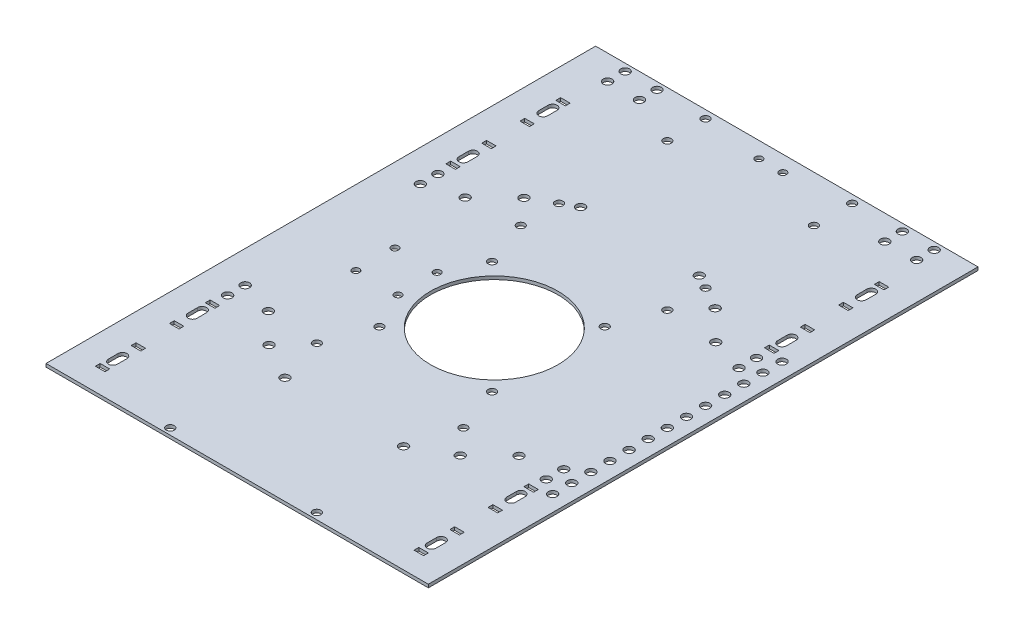
SolidWorks part; units mm, degrees
ref_plane "前视基准面" through (0, 0, 0) normal (0, 0, 1) x (1, 0, 0)
ref_plane "上视基准面" through (0, 0, 0) normal (0, 1, 0) x (1, 0, 0)
ref_plane "右视基准面" through (0, 0, 0) normal (1, 0, 0) x (0, 0, -1)
sketch "草图1" plane through (0, 0, 0) normal (0, 1, 0) x (1, 0, 0)
  line L2 (-120, 140) -> (-120, -140)
  line L3 (-120, -140) -> (120, -140)
  line L4 (120, 140) -> (120, -140)
  line L5 (-120, 140) -> (120, -140) construction
  line L6 (-120, -140) -> (120, 140) construction
  line L7 (-120, 185) -> (120, 185)
  line L8 (-120, 185) -> (-120, 140)
  line L10 (120, 185) -> (120, 140)
  line L11 (-120, 185) -> (120, 140) construction
  line L12 (-120, 140) -> (120, 185) construction
  point P0 (0, 0)
  point P6 (0, 162.5)
  dimension "D1" = 240
  dimension "D2" = 280
  dimension "D3" = 45
base flange "基体-法兰1" sketch "草图1" thickness 2 reverse thickness direction no parameters "D1"=2.7366
sketch "草图6" plane through (0, 0, 0) normal (0, 1, 0) x (1, 0, 0)
  line L0 (0, 0) -> (170.3975, 0) construction
  line L1 (0, 0) -> (0, -100) construction
  circle A0 centre (0, 0) radius 100 construction
  circle A1 centre (-60, -80) radius 2.75
  circle A2 centre (-78.6611, -61.7449) radius 2.75
  circle A3 centre (-37.25, -92.8032) radius 2.75
  circle A4 centre (37.25, -92.8032) radius 2.75
  circle A5 centre (78.6611, -61.7449) radius 2.75
  circle A6 centre (60, -80) radius 2.75
  circle A7 centre (78.6611, 61.7449) radius 2.75
  circle A8 centre (37.25, 92.8032) radius 2.75
  circle A9 centre (-60, 80) radius 2.75
  circle A10 centre (60, 80) radius 2.75
  circle A11 centre (-78.6611, 61.7449) radius 2.75
  circle A12 centre (-37.25, 92.8032) radius 2.75
  point P10 (0, 0)
  point P12 (0, 0)
  point P13 (0, 0)
  point P15 (0, 0)
  dimension "D1" = 200
  dimension "D2" = 5.5
  dimension "D3" = 80
  dimension "D4" = 2
  dimension "D5" = 2
extrude "切除-拉伸1" cut sketch "草图6" against normal blind 10 normal cut yes
sketch "草图7" plane through (0, 0, 0) normal (0, 1, 0) x (1, 0, 0)
  circle A0 centre (0, 0) radius 50 construction
  circle A1 centre (-35.3553, 35.3553) radius 2.5
  circle A2 centre (35.3553, 35.3553) radius 2.5
  circle A3 centre (35.3553, -35.3553) radius 2.5
  circle A4 centre (-35.3553, -35.3553) radius 2.5
  circle A5 centre (1.3845, 0) radius 40
  dimension "D2" = 100
  dimension "D3" = 5
  dimension "D1" = 80
  dimension "D4" = 4
extrude "切除-拉伸2" cut sketch "草图7" against normal blind 10 normal cut yes
sketch "草图9" plane through (0, 0, 0) normal (0, 1, 0) x (1, 0, 0)
  line L0 (120, -140) -> (120, 185) construction
  line L1 (-120, -140) -> (120, -140)
  line L2 (-120, -140) -> (-120, -160)
  line L3 (-120, -160) -> (120, -160)
  line L4 (120, -140) -> (120, -160)
  dimension "D1" = 20
extrude "凸台-拉伸1" add sketch "草图9" against normal blind 2
extrude "切除-拉伸3" cut sketch "草图8" against normal blind 10 normal cut yes
sketch "草图8" plane through (0, 0, 0) normal (0, 1, 0) x (1, 0, 0)
  line L0 (120, -160) -> (120, 185) construction
  line L1 (100, -110) -> (120, -110) construction
  line L2 (0, 0) -> (0, -160) construction
  line L3 (0, 0) -> (-120, 0) construction
  line L4 (-120, 185) -> (-120, -160) construction
  line L5 (100, -132) -> (100, -138) construction
  line L6 (110, -120) -> (90, -120) construction
  line L7 (110, -120) -> (110, -100) construction
  line L8 (110, -100) -> (90, -100) construction
  line L9 (90, -120) -> (90, -100) construction
  line L10 (110, -120) -> (90, -100) construction
  line L11 (110, -100) -> (90, -120) construction
  line L12 (102.8, -132) -> (102.8, -138)
  line L13 (97.2, -132) -> (97.2, -138)
  line L14 (-120, -160) -> (120, -160) construction
  line L15 (103, -146) -> (97, -146)
  line L16 (103, -146) -> (103, -143)
  line L17 (103, -143) -> (97, -143)
  line L18 (97, -146) -> (97, -143)
  line L19 (103, -146) -> (97, -143) construction
  line L20 (103, -143) -> (97, -146) construction
  line L21 (103, -123.5) -> (97, -123.5)
  line L22 (103, -123.5) -> (103, -120.5)
  line L23 (103, -120.5) -> (97, -120.5)
  line L24 (97, -123.5) -> (97, -120.5)
  line L25 (103, -123.5) -> (97, -120.5) construction
  line L26 (103, -120.5) -> (97, -123.5) construction
  line L27 (120, -160) -> (120, 185) construction
  line L28 (103, -99.5) -> (97, -96.5) construction
  line L29 (103, -96.5) -> (97, -99.5) construction
  line L30 (103, -77) -> (97, -74) construction
  line L31 (103, -74) -> (97, -77) construction
  line L32 (97, -96.5) -> (97, -99.5)
  line L33 (103, -99.5) -> (97, -99.5)
  line L34 (103, -96.5) -> (103, -99.5)
  line L35 (103, -96.5) -> (97, -96.5)
  line L36 (97, -74) -> (97, -77)
  line L37 (103, -77) -> (97, -77)
  line L38 (103, -74) -> (103, -77)
  line L39 (103, -74) -> (97, -74)
  line L40 (100, -88) -> (100, -82) construction
  line L41 (102.8, -88) -> (102.8, -82)
  line L42 (97.2, -88) -> (97.2, -82)
  arc A0 (102.8, -88) -> (97.2, -88) centre (100, -88) cw
  arc A1 (97.2, -82) -> (102.8, -82) centre (100, -82) cw
  arc A2 (102.8, -132) -> (97.2, -132) centre (100, -132) ccw
  arc A3 (97.2, -138) -> (102.8, -138) centre (100, -138) ccw
  circle A4 centre (100, -66) radius 2.75
  circle A5 centre (100, -55) radius 2.75
  point P11 (100, -110)
  point P21 (100, -135)
  point P26 (100, -144.5)
  point P31 (100, -122)
  point P44 (100, -98)
  point P45 (100, -75.5)
  point P48 (100, -85)
  dimension "D9" = 2.8
  dimension "D17" = 5.5
  dimension "D2" = 19
  dimension "D3" = 25
  dimension "D5" = 20
  dimension "D6" = 20
  dimension "D7" = 110
  dimension "D8" = 10
  dimension "D10" = 6
  dimension "D11" = 6
  dimension "D12" = 6.5
  dimension "D13" = 3
  dimension "D14" = 10
  dimension "D15" = 3
  dimension "D16" = 6
  dimension "D4" = 11
mirror "镜向1" about plane through (0, 0, 0) normal (0, 0, 1) of "切除-拉伸3"
mirror "镜向2" about plane through (0, 0, 0) normal (1, 0, 0) of "镜向1", "切除-拉伸3"
sketch "草图10" plane through (0, 0, 0) normal (0, 1, 0) x (1, 0, 0)
  line L0 (120, 185) -> (-120, 185) construction
  line L1 (-120, 185) -> (-120, -160) construction
  circle A0 centre (-97, 180.5) radius 2.75
  circle A1 centre (-77, 180.5) radius 2.75
  circle A2 centre (-97, 169.5) radius 2.75
  circle A3 centre (-77, 169.5) radius 2.75
  dimension "D3" = 5.5
  dimension "D4" = 20
  dimension "D1" = 4.5
  dimension "D2" = 23
  dimension "D5" = 2
extrude "切除-拉伸4" cut sketch "草图10" against normal blind 10 normal cut yes
mirror "镜向3" about plane through (0, 0, 0) normal (1, 0, 0) of "切除-拉伸4"
sketch "草图11" plane through (0, 0, 0) normal (0, 1, 0) x (1, 0, 0)
  line L0 (120, -160) -> (120, 185) construction
  circle A0 centre (110, 72) radius 2.75
  circle A1 centre (110, 60) radius 2.75
  circle A2 centre (110, 48) radius 2.75
  circle A3 centre (110, 36) radius 2.75
  circle A4 centre (110, 24) radius 2.75
  circle A5 centre (110, 12) radius 2.75
  circle A6 centre (110, 0) radius 2.75
  circle A7 centre (110, -12) radius 2.75
  circle A8 centre (110, -24) radius 2.75
  circle A9 centre (110, -36) radius 2.75
  circle A10 centre (110, -48) radius 2.75
  circle A11 centre (110, -60) radius 2.75
  circle A12 centre (110, -72) radius 2.75
  dimension "D2" = 5.5
  dimension "D1" = 10
  dimension "D4" = 72
  dimension "D3" = 13
extrude "切除-拉伸5" cut sketch "草图11" against normal blind 10 normal cut yes
sketch "草图12" plane through (0, 0, 0) normal (0, 1, 0) x (1, 0, 0)
  line L0 (-46.75, 0) -> (-73.25, 0) construction
  line L1 (-120, 185) -> (-120, -160) construction
  line L2 (0, 185) -> (0, 140.1837) construction
  line L3 (120, 185) -> (-120, 185) construction
  circle A0 centre (-73.25, 12.25) radius 2.25
  circle A1 centre (-73.25, -12.25) radius 2.25
  circle A2 centre (-46.75, 12.25) radius 2.25
  circle A3 centre (-46.75, -12.25) radius 2.25
  circle A4 centre (7.5, 175) radius 2.25
  circle A5 centre (-7.5, 175) radius 2.25
  point P16 (-60, 0)
  dimension "D3" = 4.5
  dimension "D5" = 4.5
  dimension "D1" = 24.5
  dimension "D4" = 60
  dimension "D6" = 15
  dimension "D7" = 10
  dimension "D8" = 26.5
  dimension "D2" = 2
extrude "切除-拉伸6" cut sketch "草图12" against normal blind 10 normal cut yes
sketch "草图13" plane through (0, 0, 0) normal (0, 1, 0) x (1, 0, 0)
  line L0 (0, 185) -> (0, 0) construction
  line L1 (0, 0) -> (-120, 0) construction
  line L2 (-46, 110) -> (0, 110) construction
  line L3 (120, 185) -> (-120, 185) construction
  line L4 (-120, 185) -> (-120, -160) construction
  circle A0 centre (-46, 156) radius 2.5
  circle A1 centre (-46, 64) radius 2.5
  circle A2 centre (46, 64) radius 2.5
  circle A3 centre (46, 156) radius 2.5
  dimension "D3" = 5
  dimension "D1" = 92
  dimension "D2" = 92
  dimension "D4" = 110
extrude "切除-拉伸7" cut sketch "草图13" against normal blind 3 normal cut yes
mirror "镜向4" about plane through (0, 0, 0) normal (0, 0, 1) of "切除-拉伸7"
sketch "草图14" plane through (0, 0, 0) normal (0, 1, 0) x (1, 0, 0)
  line L0 (-44, 134) -> (0, 134) construction
  line L1 (0, 134) -> (0, 185) construction
  line L2 (120, 185) -> (-120, 185) construction
  circle A0 centre (-46, 180) radius 2.5
  circle A1 centre (-46, 88) radius 2.5
  circle A2 centre (46, 88) radius 2.5
  circle A3 centre (46, 180) radius 2.5
  dimension "D4" = 5
  dimension "D1" = 92
  dimension "D2" = 92
  dimension "D3" = 5
extrude "切除-拉伸8" cut sketch "草图14" against normal blind 10 normal cut yes
sketch "折弯-线1" plane through (0, 0, 0) normal (0, 1, 0) x (1, 0, 0)
sketch "边界框1" plane through (0, 0, 0) normal (0, 1, 0) x (1, 0, 0)
sheet metal parameters "钣金6" thickness 2 parameters "D1"=2.7366
flat pattern "平板型式6" [suppressed]
sketch "折弯-线2" plane through (0, 0, 0) normal (0, 1, 0) x (1, 0, 0)
sketch "边界框2" [suppressed] plane through (0, 0, 0) normal (0, 1, 0) x (1, 0, 0)
sheet metal parameters "钣金7" thickness 2 parameters "D1"=2.7366
flat pattern "平板型式6"
sketch "折弯-线2" plane through (0, 0, 0) normal (0, 1, 0) x (1, 0, 0)
sketch "边界框2" [suppressed] plane through (0, 0, 0) normal (0, 1, 0) x (1, 0, 0)
sheet metal parameters "钣金8" thickness 2 parameters "D1"=2.7366
flat pattern "平板型式6"
sketch "折弯-线2" plane through (0, 0, 0) normal (0, 1, 0) x (1, 0, 0)
sketch "边界框2" [suppressed] plane through (0, 0, 0) normal (0, 1, 0) x (1, 0, 0)
sheet metal parameters "钣金11" thickness 2 parameters "D1"=2.7366
flat pattern "平板型式6"
sketch "折弯-线2" plane through (0, 0, 0) normal (0, 1, 0) x (1, 0, 0)
sketch "边界框2" [suppressed] plane through (0, 0, 0) normal (0, 1, 0) x (1, 0, 0)
sheet metal parameters "钣金12" thickness 2 parameters "D1"=2.7366
flat pattern "平板型式6"
sketch "折弯-线2" plane through (0, 0, 0) normal (0, 1, 0) x (1, 0, 0)
sketch "边界框2" [suppressed] plane through (0, 0, 0) normal (0, 1, 0) x (1, 0, 0)
sheet metal parameters "钣金13" thickness 2 parameters "D1"=2.7366
flat pattern "平板型式6"
sketch "折弯-线2" plane through (0, 0, 0) normal (0, 1, 0) x (1, 0, 0)
sketch "边界框2" [suppressed] plane through (0, 0, 0) normal (0, 1, 0) x (1, 0, 0)
sheet metal parameters "钣金14" thickness 2 parameters "D1"=2.7366
flat pattern "平板型式6"
sketch "折弯-线2" plane through (0, 0, 0) normal (0, 1, 0) x (1, 0, 0)
sketch "边界框2" [suppressed] plane through (0, 0, 0) normal (0, 1, 0) x (1, 0, 0)
sheet metal parameters "钣金15" thickness 2 parameters "D1"=2.7366
flat pattern "平板型式6"
sketch "折弯-线2" plane through (0, 0, 0) normal (0, 1, 0) x (1, 0, 0)
sketch "边界框2" [suppressed] plane through (0, 0, 0) normal (0, 1, 0) x (1, 0, 0)
sheet metal parameters "钣金16" thickness 2 parameters "D1"=2.7366
flat pattern "平板型式6"
sketch "折弯-线2" plane through (0, 0, 0) normal (0, 1, 0) x (1, 0, 0)
sketch "边界框2" [suppressed] plane through (0, 0, 0) normal (0, 1, 0) x (1, 0, 0)
sheet metal parameters "钣金17" thickness 2 parameters "D1"=2.7366
flat pattern "平板型式6"
sketch "折弯-线2" plane through (0, 0, 0) normal (0, 1, 0) x (1, 0, 0)
sketch "边界框2" [suppressed] plane through (0, 0, 0) normal (0, 1, 0) x (1, 0, 0)
sheet metal parameters "钣金18" thickness 2 parameters "D1"=2.7366
flat pattern "平板型式6"
sketch "折弯-线2" plane through (0, 0, 0) normal (0, 1, 0) x (1, 0, 0)
sketch "边界框2" [suppressed] plane through (0, 0, 0) normal (0, 1, 0) x (1, 0, 0)
sheet metal parameters "钣金19" thickness 2 parameters "D1"=2.7366
flat pattern "平板型式6"
sketch "折弯-线2" plane through (0, 0, 0) normal (0, 1, 0) x (1, 0, 0)
sketch "边界框2" [suppressed] plane through (0, 0, 0) normal (0, 1, 0) x (1, 0, 0)
sheet metal parameters "钣金20" thickness 2 parameters "D1"=2.7366
flat pattern "平板型式6"
sketch "折弯-线2" plane through (0, 0, 0) normal (0, 1, 0) x (1, 0, 0)
sketch "边界框2" [suppressed] plane through (0, 0, 0) normal (0, 1, 0) x (1, 0, 0)
sheet metal parameters "钣金21" thickness 2 parameters "D1"=2.7366
flat pattern "平板型式6"
sketch "折弯-线2" plane through (0, 0, 0) normal (0, 1, 0) x (1, 0, 0)
sketch "边界框2" [suppressed] plane through (0, 0, 0) normal (0, 1, 0) x (1, 0, 0)
